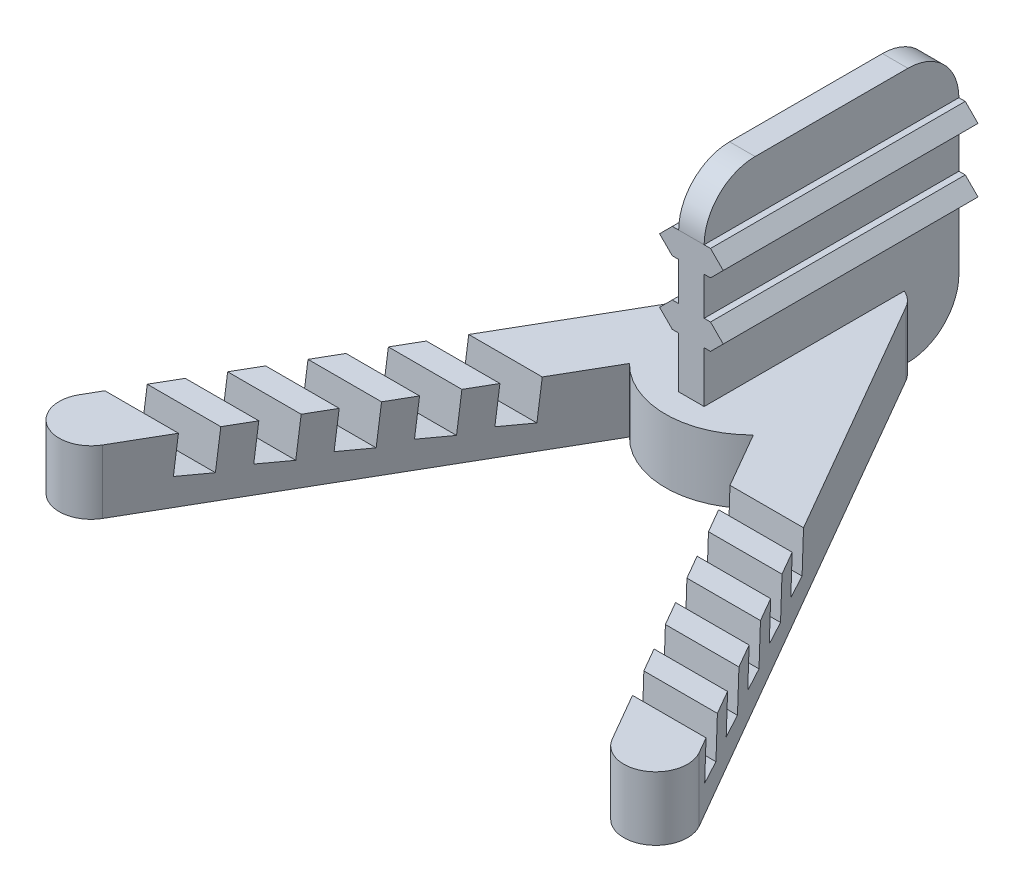
SolidWorks part; units mm, degrees
ref_plane "Front Plane" through (0, 0, 0) normal (0, 0, 1) x (1, 0, 0)
ref_plane "Top Plane" through (0, 0, 0) normal (0, 1, 0) x (1, 0, 0)
ref_plane "Right Plane" through (0, 0, 0) normal (1, 0, 0) x (0, 0, -1)
sketch "Sketch1" plane through (0, 0, 0) normal (0, 1, 0) x (1, 0, 0)
  line L0 (0, 0) -> (0, 34.641) construction
  line L3 (0, 34.641) -> (-20, 0) construction
  line L6 (-20, 0) -> (20, 0) construction
  line L9 (0, 39.641) -> (0, 29.641) construction
  line L10 (-20, 0) -> (0, 34.641) construction
  line L13 (-24.3301, -2.5) -> (-2.1651, 35.891)
  line L14 (-20, -5) -> (-2.1651, 25.891)
  line L15 (0, 39.641) -> (0, 29.641) construction
  line L18 (-20, 0) -> (-20, -5) construction
  line L19 (-24.3301, -2.5) -> (-20, -5) construction
  line L22 (24.3301, -2.5) -> (2.1651, 35.891)
  line L23 (20, -5) -> (2.1651, 25.891)
  arc A10 (-24.3301, -2.5) -> (-20, -5) centre (-22.1651, -3.75) ccw
  arc A11 (24.3301, -2.5) -> (20, -5) centre (22.1651, -3.75) cw
  arc A12 (2.1651, 25.891) -> (-2.1651, 25.891) centre (0, 24.641) ccw
  arc A13 (-2.1651, 35.891) -> (2.1651, 35.891) centre (0, 34.641) cw
  point P5 (0, 34.641)
  dimension "D3" = 5
  dimension "D4" = 2.5
  dimension "LegSpacing" = 20
  dimension "D2" = 30
extrude "Base" add sketch "Sketch1" along normal blind 5 contours L23 L13 L14 region at (-12.6786, 0, -16.367)
sketch "Sketch2" plane through (0, 0, 0) normal (1, 0, 0) x (0, 0, -1)
  line L0 (-1.4818, 2.1105) -> (-0.6102, 12.0725)
  line L1 (-1.4818, 2.1105) -> (0.6102, 1.9275)
  line L2 (-0.6102, 12.0725) -> (1.4818, 11.8895)
  line L3 (0.6102, 1.9275) -> (1.4818, 11.8895)
  line L4 (-1.4818, 2.1105) -> (1.4818, 11.8895) construction
  line L5 (-0.6102, 12.0725) -> (0.6102, 1.9275) construction
  line L6 (3.3898, 12.0725) -> (5.4818, 11.8895)
  line L7 (2.5182, 2.1105) -> (3.3898, 12.0725)
  line L8 (4.6102, 1.9275) -> (5.4818, 11.8895)
  line L9 (2.5182, 2.1105) -> (5.4818, 11.8895) construction
  line L10 (23.8651, 0) -> (-23.8651, 0) construction
  line L11 (3.3898, 12.0725) -> (4.6102, 1.9275) construction
  line L12 (2.5182, 2.1105) -> (4.6102, 1.9275)
  line L31 (7.3898, 12.0725) -> (9.4818, 11.8895)
  line L36 (6.5182, 2.1105) -> (7.3898, 12.0725)
  line L42 (8.6102, 1.9275) -> (9.4818, 11.8895)
  line L43 (6.5182, 2.1105) -> (9.4818, 11.8895) construction
  line L48 (7.3898, 12.0725) -> (8.6102, 1.9275) construction
  line L49 (6.5182, 2.1105) -> (8.6102, 1.9275)
  line L62 (11.3898, 12.0725) -> (13.4818, 11.8895)
  line L63 (10.5182, 2.1105) -> (11.3898, 12.0725)
  line L68 (12.6102, 1.9275) -> (13.4818, 11.8895)
  line L69 (10.5182, 2.1105) -> (13.4818, 11.8895) construction
  line L71 (11.3898, 12.0725) -> (12.6102, 1.9275) construction
  line L72 (10.5182, 2.1105) -> (12.6102, 1.9275)
  line L73 (15.3898, 12.0725) -> (17.4818, 11.8895)
  line L74 (14.5182, 2.1105) -> (15.3898, 12.0725)
  line L75 (16.6102, 1.9275) -> (17.4818, 11.8895)
  line L76 (14.5182, 2.1105) -> (17.4818, 11.8895) construction
  line L77 (15.3898, 12.0725) -> (16.6102, 1.9275) construction
  line L78 (14.5182, 2.1105) -> (16.6102, 1.9275)
  point P1 (0, 7)
  dimension "D1" = 2.1
  dimension "D3" = 5
  dimension "D2" = 85
  dimension "D4" = 7
  dimension "D5" = 5
extrude "BoardSlot" cut sketch "Sketch2" against normal through all both and the other way through all
sketch "Sketch3" plane through (0, 0, 0) normal (0, 1, 0) x (1, 0, 0)
  line L0 (-22.3792, 0.879) -> (-21.2869, 2.771) construction
  line L4 (-22.3792, 0.879) -> (-13.1416, 16.879) construction
  line L5 (22.1184, 1.3308) -> (13.1416, 16.879) construction
  line L6 (13.1416, 16.879) -> (2.1651, 35.891) construction
  line L7 (-13.1416, 16.879) -> (-2.1651, 35.891) construction
  line L8 (5.9067, 29.4103) -> (2.1651, 35.891)
  line L9 (-5.9067, 29.4103) -> (-2.1651, 35.891)
  line L10 (-13.1416, 16.879) -> (-5.9067, 29.4103) construction
  line L11 (-13.1416, 16.879) -> (-5.9067, 29.4103) construction
  line L12 (13.1416, 16.879) -> (5.9067, 29.4103) construction
  line L13 (13.1416, 16.879) -> (5.9067, 29.4103) construction
  arc A1 (-5.9067, 29.4103) -> (5.9067, 29.4103) centre (0, 26) ccw
  circle A3 centre (0, 26) radius 5 construction
  arc A6 (5.9067, 29.4103) -> (-5.9067, 29.4103) centre (0, 26) ccw construction
  arc A7 (2.1651, 35.891) -> (-2.1651, 35.891) centre (0, 34.641) ccw construction
  arc A8 (2.1651, 35.891) -> (-2.1651, 35.891) centre (0, 34.641) ccw
  dimension "D1" = 10
  dimension "D2" = 26
extrude "SupportMount" add sketch "Sketch3" along normal blind 5 contours A1 A3 region at (0, 0, -27.2909)
ref_plane "Plane1" through (0, 0, -37.141) normal (0, 0, -1) x (-1, 0, 0)
sketch "Sketch7" plane through (0, 0, 0) normal (0, 1, 0) x (1, 0, 0)
  line L5 (3, 23) -> (-3, 23)
  line L6 (3, 23) -> (3, 29)
  line L8 (3, 29) -> (-3, 29)
  line L10 (-3, 23) -> (-3, 29)
  line L12 (3, 23) -> (-3, 29) construction
  line L13 (3, 29) -> (-3, 23) construction
  point P0 (0, 26)
  dimension "D1" = 26
  dimension "D2" = 6
extrude "SupportInsert" [suppressed] cut sketch "Sketch7" along normal through all
sketch "Sketch9" plane through (0, 0, 0) normal (1, 0, 0) x (0, 0, -1)
  line L0 (-2.5, 0) -> (35.891, 0) construction
  line L1 (21.2178, 0) -> (37.2178, 0)
  line L2 (21.2178, 0) -> (21.2178, 16)
  line L3 (25.2178, 20) -> (37.2178, 20)
  line L4 (41.2178, 4) -> (41.2178, 16)
  arc A0 (37.2178, 0) -> (41.2178, 4) centre (37.2178, 4) ccw
  arc A1 (37.2178, 20) -> (41.2178, 16) centre (37.2178, 16) cw
  arc A2 (21.2178, 16) -> (25.2178, 20) centre (25.2178, 16) cw
  point P9 (41.2178, 0)
  point P12 (41.2178, 20)
  dimension "D3" = 4
  dimension "D1" = 20
  dimension "D2" = 20
extrude "Boss-Extrude1" add sketch "Sketch9" along normal mid plane 2
sketch "Sketch10" plane through (0, 0, 0) normal (1, 0, 0) x (0, 0, -1)
  line L0 (31.2178, 20) -> (31.2178, 15) construction
  line L1 (37.2178, 20) -> (25.2178, 20) construction
  line L2 (31.2178, 15) -> (31.2178, 10) construction
  line L3 (31.2178, 10) -> (31.2178, 5) construction
  line L4 (16.879, 5) -> (35.891, 5) construction
  line L5 (21.2178, 16) -> (21.2178, 5) construction
  line L6 (41.2178, 14) -> (21.2178, 14)
  line L7 (41.2178, 14) -> (41.2178, 16)
  line L8 (41.2178, 16) -> (21.2178, 16)
  line L9 (21.2178, 14) -> (21.2178, 16)
  line L10 (41.2178, 14) -> (21.2178, 16) construction
  line L11 (41.2178, 16) -> (21.2178, 14) construction
  line L12 (41.2178, 9) -> (21.2178, 9)
  line L13 (41.2178, 9) -> (41.2178, 11)
  line L14 (41.2178, 11) -> (21.2178, 11)
  line L15 (21.2178, 9) -> (21.2178, 11)
  line L16 (41.2178, 9) -> (21.2178, 11) construction
  line L17 (41.2178, 11) -> (21.2178, 9) construction
  dimension "D1" = 2
extrude "Boss-Extrude2" add sketch "Sketch10" along normal mid plane 5 contours L8 | L9 L6 L7 L8 | L15 L12 L13 L14 region at (0, 15, -31.2178) region at (0, 10, -31.2178)
chamfer "Chamfer1" distance 1 angle 45 8 edges at (-2.5, 9, -31.2178) (-2.5, 11, -31.2178) (-2.5, 14, -31.2178) (-2.5, 16, -31.2178) (2.5, 9, -31.2178) (2.5, 11, -31.2178) (2.5, 14, -31.2178) (2.5, 16, -31.2178)
sketch "Sketch8" plane through (0, 0, 0) normal (0, 0, 1) x (1, 0, 0)
  circle A0 centre (0, 2.5) radius 1.4
  dimension "D2" = 2.8
  dimension "D1" = 2.5
extrude "ScrewHole" [suppressed] cut sketch "Sketch8" against normal offset from surface (32.141 mm away) 5
equation "\"BoardReclineAngle\"= 85"
equation "\"FrontProtrusion\"=10"
equation "\"HolderSlotThickness\"=2.1"
equation "\"D1@Sketch2\"=\"HolderSlotThickness\""
equation "\"LegWidth\"= 60"
equation "\"LegAngle\"= 60"
equation "\"D2@Sketch1\"=\"LegAngle\"/2"
equation "\"LegThickness\"= 5"
equation "\"D3@Sketch1\"=\"LegThickness\""
equation "\"D4@Sketch1\"=\"LegThickness\"/2"
equation "\"D1@Base\"=\"LegThickness\""
equation "\"D1@Sketch7\"=\"D2@Sketch3\""
equation "\"D2@Sketch3\"=\"LegSpacing@Sketch1\"*1.3"
equation "\"D1@Sketch8\"=\"D1@Base\"/2"
equation "\"D1@SupportMount\"=\"D3@Sketch1\""
equation "\"D4@Sketch2\"=\"D3@Sketch2\"+2"
